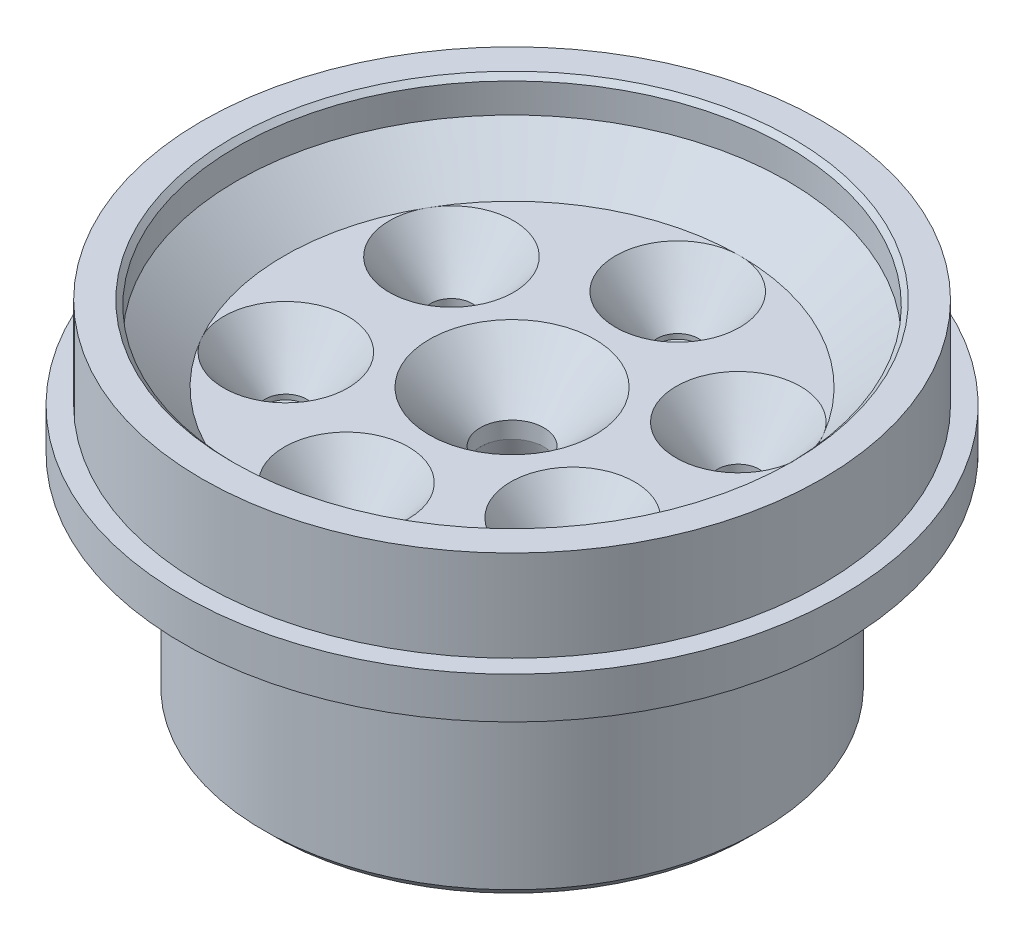
SolidWorks part; units mm, degrees
ref_plane "Front Plane" through (0, 0, 0) normal (0, 0, 1) x (1, 0, 0)
ref_plane "Top Plane" through (0, 0, 0) normal (0, 1, 0) x (1, 0, 0)
ref_plane "Right Plane" through (0, 0, 0) normal (1, 0, 0) x (0, 0, -1)
sketch "Sketch1" plane through (0, 0, 0) normal (0, 0, 1) x (1, 0, 0)
  line L0 (0, 0) -> (0, 30.0211)
  line L1 (0, 0) -> (19.05, 0)
  line L2 (19.05, 0) -> (19.05, 14.5288)
  line L3 (25.273, 16.3068) -> (22.2123, 16.3068)
  line L4 (19.05, 14.5288) -> (22.2123, 14.5288)
  line L5 (22.2123, 14.5288) -> (22.2123, 16.3068)
  line L6 (25.273, 16.3068) -> (25.273, 19.4818)
  line L7 (25.273, 19.4818) -> (23.7744, 19.4818)
  line L8 (23.7744, 19.4818) -> (23.7744, 26.4668)
  line L9 (23.7744, 26.4668) -> (21.1074, 26.4668)
  line L10 (21.1074, 26.4668) -> (21.1074, 23.8252)
  line L11 (21.1074, 23.8252) -> (17.4625, 20.6756)
  line L12 (17.4625, 20.6756) -> (0, 20.6756)
  dimension "D1" = 3.175
  dimension "D2" = 1.4986
  dimension "D3" = 2.667
  dimension "D4" = 3.0607
  dimension "D5" = 14.5288
  dimension "D6" = 25.273
  dimension "D7" = 19.05
  dimension "D8" = 26.4668
  dimension "D9" = 2.6416
  dimension "D10" = 17.4625
  dimension "D11" = 3.1496
revolve "Revolve1" add sketch "Sketch1" angle 360 about L0 region at (10.9556, 11.4644, 0)
chamfer "Chamfer1" distance 0.381 angle 45 1 edges at (0, 26.4668, -21.1074)
chamfer "Chamfer2" distance 0.762 angle 45 1 edges at (0, 0, -19.05)
sketch "Sketch2" plane through (0, 20.6756, 0) normal (0, 1, 0) x (1, 0, 0)
  line L0 (0, 0) -> (0, 17.4625) construction
  circle A6 centre (0, 12.7) radius 4.7625
  dimension "D1" = 9.525
chamfer "Chamfer4" distance 1.27 angle 45 1 edges at (0, 14.5288, -19.05)
ref_plane "Plane2" through (0, 16.764, 0) normal (0, 1, 0) x (1, 0, 0)
sketch "Sketch3" plane through (0, 16.764, 0) normal (0, 1, 0) x (1, 0, 0)
  circle A0 centre (0, 12.7) radius 1.5875
  dimension "D1" = 3.175
loft "Cut-Loft1" cut profiles "Sketch3", "Sketch2" connector at (0, 16.764, -11.1125) connector at (0, 20.6756, -7.9375)
sketch "Sketch4" plane through (0, 20.6756, 0) normal (0, 1, 0) x (1, 0, 0)
  circle A0 centre (0, 0) radius 6.35
sketch "Sketch5" plane through (0, 16.764, 0) normal (0, 1, 0) x (1, 0, 0)
  circle A0 centre (0, 0) radius 2.4384
loft "Cut-Loft3" cut profiles "Sketch5", "Sketch4" connector at (0, 16.764, 2.4384) connector at (0, 20.6756, 6.35)
ref_axis "Axis2" through (0, -1.3233, 0) along (0, 1, 0)
sketch "Sketch9" plane through (0, 16.764, 0) normal (0, 1, 0) x (1, 0, 0)
  circle A0 centre (0, 0) radius 2.4384
extrude "Cut-Extrude1" cut sketch "Sketch9" against normal blind 1.27
extrude "Cut-Extrude2" cut sketch "Sketch3<3>" against normal blind 0.381
sketch "Sketch3<3>" plane through (0, 16.764, 0) normal (0, 1, 0) x (1, 0, 0) same geometry as "Sketch3"
sketch "Sketch10" plane through (0, 16.383, 0) normal (0, 1, 0) x (1, 0, 0)
  circle A0 centre (0, 12.7) radius 1.5875
extrude "Cut-Extrude3" cut sketch "Sketch10" against normal blind 0.381 draft 77
sketch "Sketch12" plane through (0, 0, 0) normal (0, -1, 0) x (1, 0, 0)
  circle A0 centre (0, 0) radius 6.35
sketch "Sketch14" plane through (0, 15.494, 0) normal (0, 1, 0) x (1, 0, 0)
  circle A0 centre (0, 0) radius 2.4384
loft "Cut-Loft5" cut profiles "Sketch14", "Sketch12" connector at (-0.1256, 15.494, -2.4352) connector at (0, 0, -6.35)
sketch "Sketch15" plane through (0, 0, 0) normal (0, -1, 0) x (1, 0, 0)
  circle A0 centre (0, -12.7) radius 4.7625
ref_plane "Plane3" through (0, 12.573, 0) normal (0, -1, 0) x (-1, 0, 0)
sketch "Sketch16" plane through (0, 12.573, 0) normal (0, -1, 0) x (-1, 0, 0)
  circle A0 centre (0, 12.7) radius 1.5875
loft "Cut-Loft7" cut profiles "Sketch16", "Sketch15" connector at (0, 12.573, -14.2875) connector at (0, 0, -17.4625)
pattern_circular "CirPattern2" count 6 over 360 about axis through (0, -1.3233, 0) along (0, 1, 0) of "Cut-Extrude2", "Cut-Extrude3", "Cut-Loft1", "Cut-Loft7"
sketch "Sketch17" plane through (0, 20.6756, 0) normal (0, 1, 0) x (1, 0, 0)
  circle A0 centre (-10.9985, 6.35) radius 1.5875
  circle A1 centre (10.9985, 6.35) radius 1.5875
  circle A2 centre (0, -12.7) radius 1.5875
extrude "Cut-Extrude4" cut sketch "Sketch17" against normal blind 25.4
